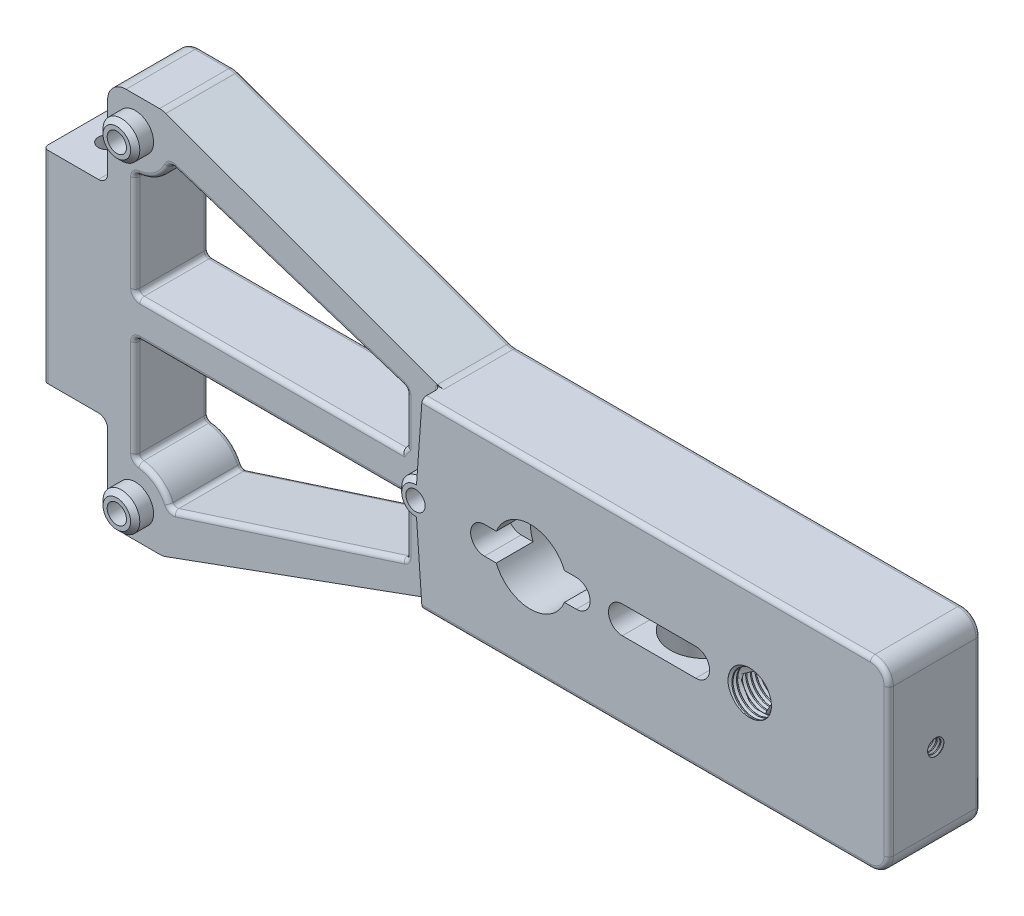
SolidWorks part; units mm, degrees
note: The reader was unsure of these and kept them because the rebuilt part matched: shared geometry of "Sketch1<3>", "Sketch1<4>", "Sketch5<3>".
ref_plane "Front Plane" through (0, 0, 0) normal (0, 0, 1) x (1, 0, 0)
ref_plane "Top Plane" through (0, 0, 0) normal (0, 1, 0) x (1, 0, 0)
ref_plane "Right Plane" through (0, 0, 0) normal (1, 0, 0) x (0, 0, -1)
sketch "Sketch1" plane through (0, 0, 0) normal (0, 0, 1) x (1, 0, 0)
  line L0 (-42, 0) -> (52, 0) construction
  line L1 (-42, 21) -> (-29, 21)
  line L2 (-42, 21) -> (-42, -21)
  line L3 (-42, -21) -> (-29, -21)
  line L4 (52, 10) -> (52, -10)
  line L5 (-42, 21) -> (42.1712, -21.0856) construction
  line L6 (-42, -21) -> (42, 21) construction
  line L7 (1.2223, 10) -> (52, 10)
  line L8 (1.2223, 10) -> (-29, 21)
  line L9 (1.2223, -10) -> (-29, -21)
  line L10 (1.2223, -10) -> (52, -10)
  line L11 (1.2223, 10) -> (0.6441, 1.9948)
  line L12 (0.6441, -1.9948) -> (1.2223, -10)
  circle A0 centre (-32, -17.5) radius 2
  circle A1 centre (-32, -17.5) radius 1.05
  circle A2 centre (-32, 17.5) radius 1.05
  circle A3 centre (-32, 17.5) radius 2
  circle A4 centre (0.5, 0) radius 2
  circle A5 centre (0.5, 0) radius 1.05
  circle A6 centre (37, 0) radius 2.5
  point P0 (0, 0)
  dimension "D4" = 4
  dimension "D5" = 2.1
  dimension "D7" = 4
  dimension "D14" = 5
  dimension "D15" = 15
  dimension "D2" = 42
  dimension "D3" = 17.5
  dimension "D6" = 10
  dimension "D9" = 32.5
  dimension "D10" = 10
  dimension "D11" = 20
  dimension "D12" = 13
  dimension "D13" = 94
  dimension "D16" = 52
extrude "Boss-Extrude1" add sketch "Sketch1" along normal blind 10 contours A4 L12 L10 L4 L7 L11 A6 | A4 A5
extrude "Boss-Extrude2" add sketch "Sketch1<3>" along normal blind 8 contours A4 L11 L8 L1 L2 L3 L9 L12 A0 A3
sketch "Sketch1<3>" plane through (0, 0, 0) normal (0, 0, 1) x (1, 0, 0) same geometry as "Sketch1"
extrude "Boss-Extrude3" add sketch "Sketch1<4>" along normal blind 10 contours A3 A2 | A0 A1
sketch "Sketch1<4>" plane through (0, 0, 0) normal (0, 0, 1) x (1, 0, 0) same geometry as "Sketch1"
sketch "Sketch2" plane through (0, -21, 0) normal (0, -1, 0) x (1, 0, 0)
  line L0 (-42, 8) -> (-42, 0) construction
  line L1 (-42, 8) -> (-29, 8) construction
  circle A0 centre (-39, 4) radius 1
  dimension "D1" = 2
  dimension "D2" = 3
  dimension "D3" = 4
extrude "Cut-Extrude1" cut sketch "Sketch2" against normal up to surface (42 mm away) up to face at (-35.5, 21, 4)
sketch "Sketch3" plane through (0, -10, 0) normal (0, -1, 0) x (1, 0, 0)
  line L0 (52, 10) -> (52, 0) construction
  line L1 (1.2223, 0) -> (52, 0) construction
  circle A0 centre (27, 5) radius 3.75
  dimension "D2" = 7.5
  dimension "D1" = 25
  dimension "D3" = 5
extrude "Cut-Extrude2" cut sketch "Sketch3" against normal blind 13
sketch "Sketch4" plane through (0, 0, 10) normal (0, 0, 1) x (1, 0, 0)
  line L0 (23, 0) -> (31, 0) construction
  line L1 (23, 1.5) -> (31, 1.5)
  line L2 (23, -1.5) -> (31, -1.5)
  line L3 (1.2223, -10) -> (52, -10) construction
  line L4 (52, 10) -> (52, -10) construction
  arc A0 (23, 1.5) -> (23, -1.5) centre (23, 0) ccw
  arc A1 (31, -1.5) -> (31, 1.5) centre (31, 0) ccw
  point P2 (27, 0)
  dimension "D1" = 1.5
  dimension "D2" = 10
  dimension "D3" = 4
  dimension "D4" = 25
sketch "Sketch5" plane through (0, 0, 10) normal (0, 0, 1) x (1, 0, 0)
  line L0 (8, 0) -> (18, 0) construction
  line L1 (8, 1.5) -> (18, 1.5)
  line L2 (8, -1.5) -> (18, -1.5)
  line L3 (-42, 21) -> (-42, -21) construction
  circle A0 centre (13, 0) radius 4
  arc A1 (8, 1.5) -> (8, -1.5) centre (8, 0) ccw
  arc A2 (18, -1.5) -> (18, 1.5) centre (18, 0) ccw
  point P4 (13, 0)
  dimension "D2" = 8
  dimension "D3" = 1.5
  dimension "D1" = 55
  dimension "D4" = 5
extrude "Cut-Extrude3" cut sketch "Sketch5" against normal blind 10 contours A0
extrude "Cut-Extrude4" cut sketch "Sketch5<3>" against normal blind 4 contours L1 A2 L2 A1
sketch "Sketch5<3>" plane through (0, 0, 10) normal (0, 0, 1) x (1, 0, 0) same geometry as "Sketch5"
extrude "Cut-Extrude5" cut sketch "Sketch4" against normal blind 6.25
sketch "Sketch12" plane through (0, -21, 0) normal (0, -1, 0) x (1, 0, 0)
  line L0 (-42, 0) -> (-29, 0) construction
  line L1 (-42, 8) -> (-35, 8)
  line L2 (-42, 8) -> (-42, 0)
  line L3 (-42, 0) -> (-35, 0)
  line L4 (-35, 8) -> (-35, 0)
  dimension "D1" = 7
extrude "Cut-Extrude11" cut sketch "Sketch12" against normal blind 10
mirror "Mirror1" about plane through (0, 0, 0) normal (0, 1, 0) of "Cut-Extrude11"
chamfer "Chamfer1" distance 0.5 3 edges at (-1.5, 0, 10) (-30, -17.5, 10) (-30, 17.5, 10)
fillet "Fillet1" radius 2 8 edges at (52, -10, 5) (52, 10, 5) (-29, -21, 4) (-29, 21, 4) (1.2223, 10, 4) (1.2223, -10, 4) (-35, 21, 4) (-35, -21, 4)
fillet "Fillet2" radius 0.5 23 edges at (1.2276, -10.0304, 0) (25.7875, -10, 0) (51.4142, -9.4142, 10) (51.4142, -9.4142, 0) (52, 0, 10) (52, 0, 0) (51.4142, 9.4142, 10) (51.4142, 9.4142, 0) (25.7875, 10, 0) (1.2276, 10.0304, 0) (-13.8889, 15.5, 0) (-29.0054, 20.9696, 0) (-31.1763, 21, 0) (-31.1763, -21, 0) (-29.0054, -20.9696, 0) (25.6111, 10, 10) (-13.8889, -15.5, 0) (25.6111, -10, 10) (-42, 0, 8) (-35, 15, 0) (-34.4142, 20.4142, 0) (-35, -15, 0) (-34.4142, -20.4142, 0)
fillet "Fillet5" radius 0.5 2 edges at (0.9332, -5.9974, 8) (0.9332, 5.9974, 8)
sketch "Sketch6" plane through (0, 0, 8) normal (0, 0, 1) x (1, 0, 0)
  line L0 (-32, 13.5) -> (-32, -13.5)
  line L3 (-2.5, 8) -> (-2.5, 2.6458)
  line L6 (-38.3662, 0) -> (0, 0) construction
  line L7 (-28.1926, 16.2739) -> (-2.5, 8)
  line L8 (-28.1926, -16.2739) -> (-2.5, -8)
  line L9 (-32, 2) -> (-2.9641, 2)
  line L10 (-32, -2) -> (-2.9641, -2)
  line L11 (-2.5, -2.6458) -> (-2.5, -8)
  arc A1 (-32, 13.5) -> (-28.1926, 16.2739) centre (-32, 17.5) ccw
  arc A2 (-28.1926, -16.2739) -> (-32, -13.5) centre (-32, -17.5) ccw
  arc A3 (-2.5, 2.6458) -> (-2.5, -2.6458) centre (0.5, 0) ccw
  dimension "D1" = 8
  dimension "D2" = 8
  dimension "D3" = 8
  dimension "D4" = 3
  dimension "D5" = 16
  dimension "D6" = 8
  dimension "D7" = 2
extrude "Cut-Extrude6" cut sketch "Sketch6" against normal up to surface (8 mm away) contours A3 L3 L7 A1 L0 L9 | A3 L10 L0 A2 L8 L11 up to face at (-9.84, 0, 0)
fillet "Fillet3" radius 0.5 33 edges at (-2.5, 5.3229, 8) (-2.5, 5.3229, 0) (-2.5, -5.3229, 8) (-2.5, -5.3229, 0) (-29.6446, -14.267, 8) (-29.6446, -14.267, 0) (-2.7481, -2.3344, 8) (-2.7481, -2.3344, 0) (-17.4821, 2, 0) (-17.4821, 2, 8) (-29.6446, 14.267, 8) (-29.6446, 14.267, 0) (-15.3463, 12.1369, 8) (-15.3463, 12.1369, 0) (-28.1926, 16.2739, 4) (-2.5, 8, 4) (-2.5, -8, 4) (-15.3463, -12.1369, 8) (-28.1926, -16.2739, 4) (-15.3463, -12.1369, 0) (-32, -13.5, 4) (-32, -7.75, 8) (-32, -7.75, 0) (-17.4821, -2, 8) (-17.4821, -2, 0) (-32, -2, 4) (-2.9641, -2, 4) (-32, 2, 4) (-32, 7.75, 8) (-32, 13.5, 4) (-32, 7.75, 0) (-2.7481, 2.3344, 8) (-2.7481, 2.3344, 0)
sketch "Sketch7" plane through (0, 0, 0) normal (0, 0, -1) x (-1, 0, 0)
  circle A0 centre (32, 17.5) radius 2
  circle A1 centre (32, -17.5) radius 2
  circle A2 centre (-0.5, 0) radius 2
  dimension "D1" = 4
extrude "Cut-Extrude7" cut sketch "Sketch7" against normal blind 3
ref_plane "Plane4" through (37, 0, 0) normal (1, 0, 0) x (0, 0, -1)
sketch "Sketch10" plane through (37, 0, 0) normal (1, 0, 0) x (0, 0, -1)
  line L0 (-15.1956, 0) -> (2.3542, 0) construction
thread "Thread1" pitch 0.5 start angle 0, offset 1, length 12, pitch 0.5, diameter 5
ref_plane "Plane1" through (34.5, 0, 11) normal (0, -1, 0) x (-1, 0, 0)
sketch "Thread Profile1" plane through (34.5, 0, 11) normal (0, -1, 0) x (-1, 0, 0)
  line L0 (0, 0) -> (0, 0.5) construction
  line L11 (0, 0) -> (0, 0.4368)
  line L12 (0, 0.4368) -> (-0.27, 0.2809)
  line L13 (-0.27, 0.2809) -> (-0.27, 0.1559)
  line L15 (-0.27, 0.1559) -> (0, 0)
  line L17 (-0.27, 0.2184) -> (0, 0.2184) construction
  point P2 (0, 0)
  dimension "Pitch" = 0.5
  dimension "Profile_Angle" = 60
  dimension "Profile_Land" = 0.125
  dimension "Profile_Height" = 0.27
sketch "Sketch11" plane through (52, 0, 0) normal (1, 0, 0) x (0, 0, -1)
  line L0 (-9.5, 10) -> (-0.5, 10) construction
  circle A0 centre (-5, 0) radius 1
  dimension "D1" = 2
  dimension "D2" = 5
  dimension "D3" = 10
extrude "Cut-Extrude10" cut sketch "Sketch11" against normal blind 10
thread "Thread4" pitch 0.4 profile "Thread Profile4" start angle 0, offset 1, length 12, pitch 0.4, diameter 2
ref_plane "Plane5" through (53, 0, 6) normal (0, -1, 0) x (0, 0, 1)
sketch "Thread Profile4" plane through (53, 0, 6) normal (0, -1, 0) x (0, 0, 1)
  line L0 (0, 0) -> (0, 0.4) construction
  line L11 (0, 0) -> (0, 0.35)
  line L12 (0, 0.35) -> (-0.2165, 0.225)
  line L13 (-0.2165, 0.225) -> (-0.2165, 0.125)
  line L15 (-0.2165, 0.125) -> (0, 0)
  line L17 (-0.2165, 0.175) -> (0, 0.175) construction
  point P2 (0, 0)
  dimension "Pitch" = 0.4
  dimension "Profile_Angle" = 60
  dimension "Profile_Land" = 0.1
  dimension "Profile_Height" = 0.2165
fillet "Fillet6" radius 1 4 edges at (-34.8536, -11, 0.1464) (-34.8536, 11, 0.1464) (-35, -11, 4.25) (-35, 11, 4.25)
